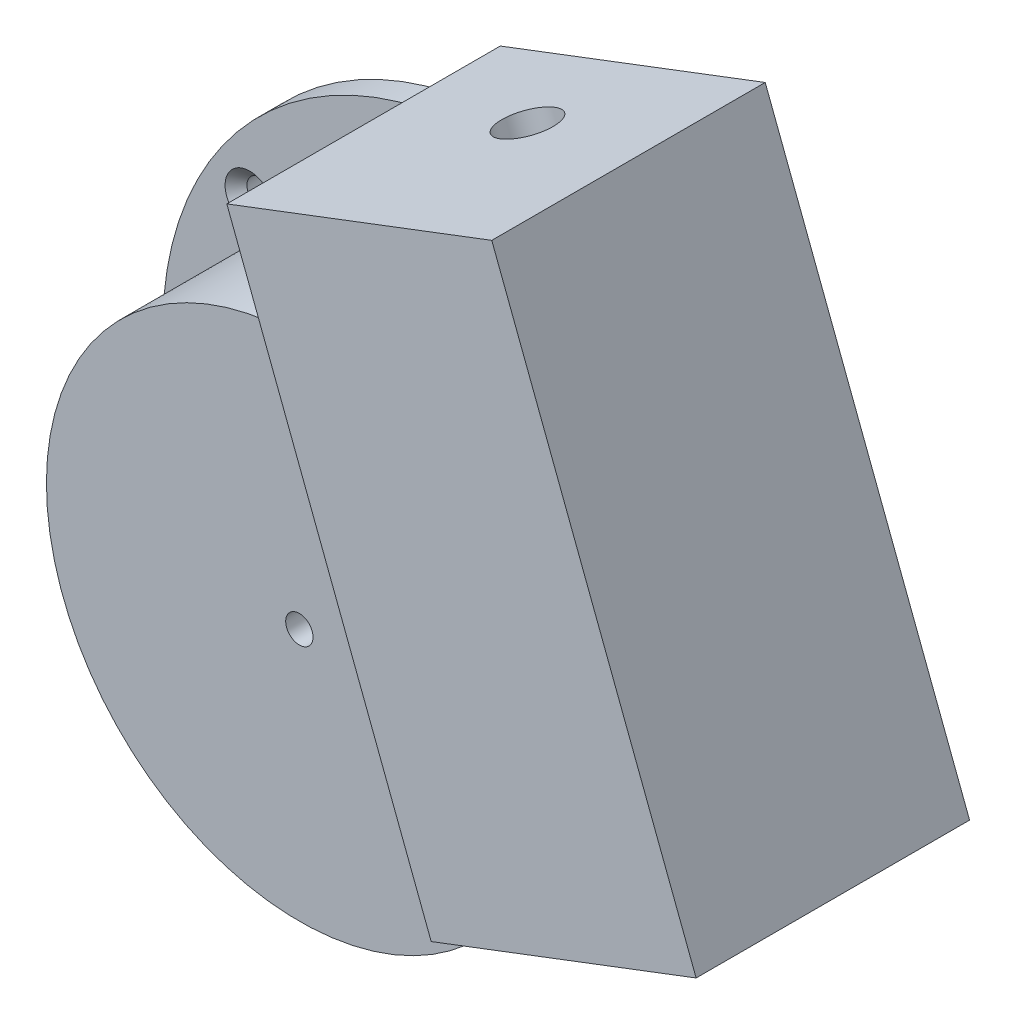
SolidWorks part; units mm, degrees
ref_plane "Piano frontale" through (0, 0, 0) normal (0, 0, 1) x (1, 0, 0)
ref_plane "Piano superiore" through (0, 0, 0) normal (0, 1, 0) x (1, 0, 0)
ref_plane "Piano destro" through (0, 0, 0) normal (1, 0, 0) x (0, 0, -1)
sketch "Schizzo1" plane through (0, 0, 0) normal (0, 0, 1) x (1, 0, 0)
  line L0 (0.3284, 23.9978) -> (-1.3054, 28.2879)
  line L1 (-1.3054, 28.2879) -> (18.0716, 35.6671)
  line L2 (18.0716, 35.6671) -> (33.0187, -3.5823)
  line L3 (33.0187, -3.5823) -> (22.8076, -7.471)
  line L6 (2.8947, 17.2589) -> (13.6417, -10.9615)
  arc A0 (2.8947, 17.2589) -> (13.6417, -10.9615) centre (0, 0) ccw
  arc A1 (0.3284, 23.9978) -> (22.8076, -7.471) centre (0, 0) ccw
  dimension "D1" = 35
  dimension "D2" = 48
extrude "Estrusione-Estrusione1" add sketch "Schizzo1" along normal blind 2
sketch "Schizzo3" plane through (0, 0, 2) normal (0, 0, 1) x (1, 0, 0)
  line L0 (13.6417, -10.9615) -> (15.3636, -10.3058)
  line L1 (22.8076, -7.471) -> (33.0187, -3.5823) construction
  line L2 (2.8947, 17.2589) -> (2.486, 18.3322)
  line L3 (-1.3054, 28.2879) -> (0.3284, 23.9978) construction
  arc A1 (2.486, 18.3322) -> (15.3636, -10.3058) centre (0, 0) ccw
  arc A2 (2.8947, 17.2589) -> (13.6417, -10.9615) centre (0, 0) ccw
  arc A3 (2.8947, 17.2589) -> (13.6417, -10.9615) centre (0, 0) ccw construction
  dimension "D1" = 37
extrude "Estrusione-Estrusione3" add sketch "Schizzo3" along normal blind 12
sketch "Schizzo5" plane through (0, 0, 2) normal (0, 0, 1) x (1, 0, 0)
  line L0 (2.8947, 17.2589) -> (8.6839, 7.6769)
  line L1 (8.6839, 7.6769) -> (1.2755, 27.1306)
  line L2 (1.2755, 27.1306) -> (16.9143, 33.0863)
  line L3 (16.9143, 33.0863) -> (30.4378, -2.4251)
  line L4 (30.4378, -2.4251) -> (12.9299, -9.0925)
  line L5 (13.6417, -10.9615) -> (12.9299, -9.0925)
  line L6 (13.6417, -10.9615) -> (33.0187, -3.5823)
  line L7 (33.0187, -3.5823) -> (18.0716, 35.6671)
  line L8 (18.0716, 35.6671) -> (-1.3054, 28.2879)
  line L9 (-1.3054, 28.2879) -> (2.8947, 17.2589)
  line L10 (13.6417, -10.9615) -> (2.8947, 17.2589) construction
  dimension "D1" = 2
  dimension "D2" = 2
  dimension "D3" = 2
  dimension "D4" = 2
extrude "Estrusione-Estrusione4" add sketch "Schizzo5" along normal blind 12
sketch "Schizzo7" plane through (0, 0, 2) normal (0, 0, 1) x (1, 0, 0)
  circle A0 centre (0, 0) radius 17.5
extrude "Taglio-Estrusione1" cut sketch "Schizzo7" against normal mid plane 24
sketch "Schizzo10" plane through (0, 0, 14) normal (0, 0, 1) x (1, 0, 0)
  line L0 (16.9143, 33.0863) -> (30.4378, -2.4251) construction
  line L1 (30.4378, -2.4251) -> (14.7989, -8.3807)
  line L2 (30.4378, -2.4251) -> (16.9143, 33.0863)
  line L3 (16.9143, 33.0863) -> (1.2755, 27.1306)
  line L4 (14.7989, -8.3807) -> (1.2755, 27.1306)
  line L5 (33.0187, -3.5823) -> (13.6417, -10.9615)
  line L6 (33.0187, -3.5823) -> (18.0716, 35.6671)
  line L7 (18.0716, 35.6671) -> (-1.3054, 28.2879)
  line L8 (13.6417, -10.9615) -> (-1.3054, 28.2879)
extrude "Estrusione-Estrusione5" add sketch "Schizzo10" along normal blind 4
sketch "Schizzo11" plane through (0, 0, 18) normal (0, 0, 1) x (1, 0, 0)
  line L0 (13.6417, -10.9615) -> (15.3636, -10.3058) construction
  line L1 (33.0187, -3.5823) -> (13.6417, -10.9615)
  line L2 (33.0187, -3.5823) -> (18.0716, 35.6671)
  line L3 (18.0716, 35.6671) -> (-1.3054, 28.2879)
  line L4 (13.6417, -10.9615) -> (-1.3054, 28.2879)
  arc A0 (2.8947, 17.2589) -> (13.6417, -10.9615) centre (0, 0) ccw construction
extrude "Estrusione-Estrusione6" add sketch "Schizzo11" along normal blind 2
sketch "Schizzo12" plane through (0, 0, 14) normal (0, 0, 1) x (1, 0, 0)
  circle A0 centre (0, 0) radius 18.5
extrude "Estrusione-Estrusione7" add sketch "Schizzo12" along normal blind 2
sketch "Schizzo13" plane through (0, 0, 16) normal (0, 0, 1) x (1, 0, 0)
  circle A0 centre (0, 0) radius 1
  dimension "D1" = 2
extrude "Taglio-Estrusione2" cut sketch "Schizzo13" against normal blind 2
sketch "Schizzo14" plane through (-9.5736, 25.1392, 0) normal (-0.3559, 0.9345, 0) x (0.9345, 0.3559, 0)
  line L0 (8.8474, -16) -> (8.8474, -18) construction
  line L1 (8.8474, -20) -> (8.8474, 0) construction
  line L2 (19.002, 0) -> (19.002, -7.5) construction
  line L4 (19.002, -7.5) -> (29.582, -7.5) construction
  line L5 (29.582, -20) -> (29.582, 0) construction
  line L7 (29.582, 0) -> (8.8474, 0) construction
  circle A1 centre (19.002, -7.5) radius 2
  dimension "D2" = 7.5
  dimension "D4" = 4
  dimension "D1" = 2
  dimension "D3" = 10.58
extrude "Taglio-Estrusione3" cut sketch "Schizzo14" against normal blind 41
sketch "Schizzo15" plane through (0, 0, 2) normal (0, 0, 1) x (1, 0, 0)
  line L0 (13.033, 20.1529) -> (-13.033, -20.1529) construction
  line L1 (-20.1529, 13.033) -> (20.1529, -13.033) construction
  line L2 (0, 0) -> (-0.8832, 23.9837) construction
  circle A0 centre (0, 0) radius 21
  arc A1 (0.3284, 23.9978) -> (22.8076, -7.471) centre (0, 0) ccw construction
  point P10 (20.4132, -12.6214)
  point P11 (-20.3484, 12.7256)
  point P13 (0, 0)
  point P14 (0, 0)
  point P15 (0, 0)
  point P16 (20.3691, -12.6926)
  point P17 (20.1529, -13.033)
  dimension "D3" = 35
  dimension "D1" = 42
  dimension "D2" = 24
  dimension "D6" = 24
hole_wizard "Foro svasato per Vite M1.6-1" positions "Schizzo3D1" profile "Schizzo16" countersink size "M1.6" standard "ISO" end condition through all
sketch3d "Schizzo3D1"
  line L0 (0, 0, 2) -> (-0.8832, 23.9837, 2) construction
  line L1 (-20.1529, 13.033, 2) -> (20.1529, -13.033, 2) construction
  line L2 (13.033, 20.1529, 2) -> (-13.033, -20.1529, 2) construction
  circle A0 centre (0, 0, 2) radius 21 construction
  point P0 (-0.7728, 20.9858, 2)
  point P6 (0, 0, 23)
  point P7 (-17.6338, 11.4039, 2)
  point P11 (-11.4039, -17.6338, 2)
  point P15 (17.6338, -11.4039, 2)
sketch "Schizzo16" plane through (-0.7728, 20.9858, 2) normal (1, 0, 0) x (0, -1, 0)
  line L0 (0, 0) -> (0, 2)
  line L1 (0, 2) -> (1, 2)
  line L2 (1, 2) -> (1, 0.8)
  line L3 (1, 0.8) -> (1.8, 0)
  line L5 (1.8, 0) -> (0, 0)
  line L6 (-1, 0.8) -> (-1.8, 0) construction
  line L11 (0, -6.35) -> (0, 107.95) construction
  dimension "Thru Hole Dia." = 2
  dimension "Thru Hole Depth" = 2
  dimension "Near C'Sink Dia." = 3.6
  dimension "Near C'Sink Angle" = 90
